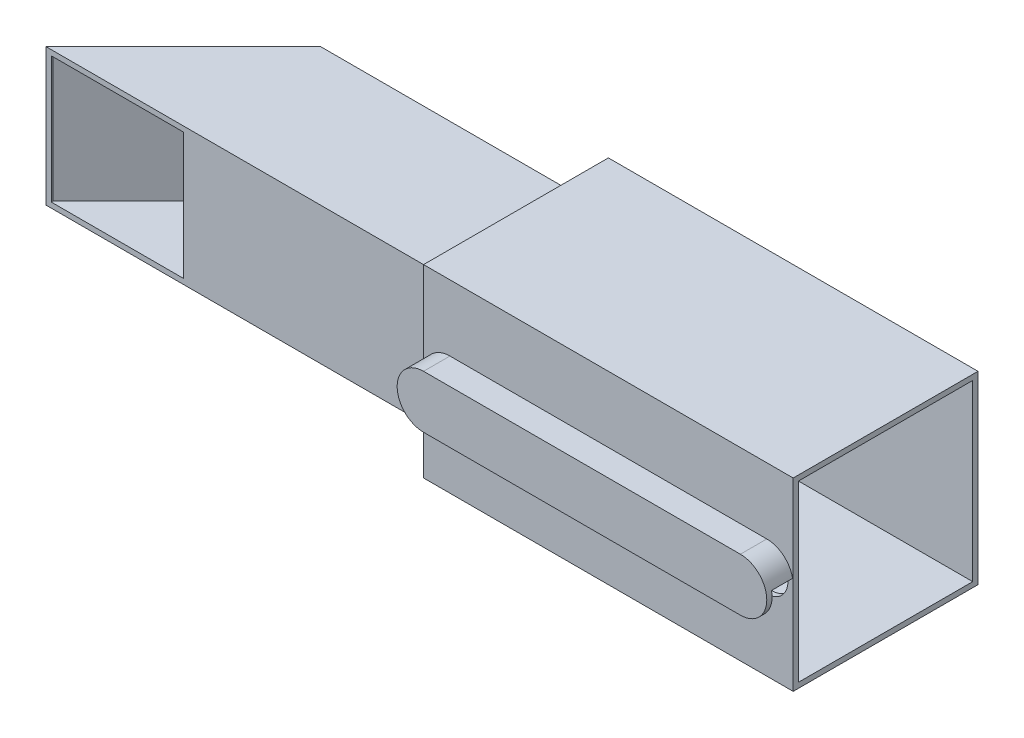
SolidWorks part; units mm, degrees
ref_plane "前视基准面" through (0, 0, 0) normal (0, 0, 1) x (1, 0, 0)
ref_plane "上视基准面" through (0, 0, 0) normal (0, 1, 0) x (1, 0, 0)
ref_plane "右视基准面" through (0, 0, 0) normal (1, 0, 0) x (0, 0, -1)
sketch "草图4" plane through (0, 0, 0) normal (0, 0, 1) x (1, 0, 0)
  line L0 (0, 17.5) -> (0, -17.5)
  line L1 (-30.7949, 0) -> (31.4954, 0) construction
  line L10 (70, 17.5) -> (70, -17.5)
  line L11 (70, -17.5) -> (0, -17.5)
  line L22 (70, 17.5) -> (0, 17.5)
  point P5 (70, 0)
  point P6 (0, 0)
  point P25 (70, 0)
  dimension "D3" = 35
  dimension "D7" = 70
extrude "凸台-拉伸6" add sketch "草图4" along normal mid plane 35
ref_plane "基准面2" through (0, 0, 22.5) normal (0, 0, 1) x (1, 0, 0)
sketch "草图6" plane through (0, 0, 22.5) normal (0, 0, 1) x (1, 0, 0)
  line L0 (72.5552, 0) -> (-4.6992, 0) construction
  line L1 (33.928, 22.6507) -> (33.928, -25.5555) construction
  line L2 (5, 5) -> (65, 5)
  line L3 (0, 17.5) -> (0, -17.5) construction
  line L4 (70, -17.5) -> (70, 17.5) construction
  line L5 (5, -5) -> (65, -5)
  arc A0 (5, 5) -> (5, -5) centre (5, 0) ccw
  arc A1 (65, -5) -> (65, 5) centre (65, 0) ccw
  dimension "D2" = 5
  dimension "D3" = 5
  dimension "D1" = 5
  dimension "D4" = 10
extrude "凸台-拉伸7" add sketch "草图6" against normal up to surface (5 mm away) up to face at (35, 0, 17.5)
shell "抽壳3" thickness 1 removed face at (70, 0, 3.5)
ref_plane "基准面3" through (5, 5, 22.5) normal (-1, 0, 0) x (0, 0, 1)
sketch "草图9" plane through (0, -5, 0) normal (0, -1, 0) x (1, 0, 0)
  line L0 (0, 21.5) -> (70, 21.5)
  line L1 (70, 17.5) -> (70, 21.5)
  line L2 (70, 17.5) -> (70, 22.5) construction
  line L3 (0, 17.5) -> (0, 21.5)
  line L4 (0, 17.5) -> (70, 17.5) construction
  line L5 (0, 17.5) -> (70, 17.5)
  dimension "D1" = 4
extrude "切除-拉伸1" cut sketch "草图9" against normal blind 6
sketch "草图22" plane through (0, 0, 0) normal (0, 0, 1) x (1, 0, 0)
  line L0 (0, -13) -> (0, 13)
  line L1 (0, 13) -> (-50, 13)
  line L2 (-50, 13) -> (-50, -13)
  line L3 (-60.5113, 0) -> (25.124, 0) construction
  line L4 (0, -13) -> (-50, -13)
  point P8 (0, 0)
  point P9 (-50, 0)
  dimension "D1" = 13
  dimension "D2" = 50
extrude "凸台-拉伸8" add sketch "草图22" along normal mid plane 26
shell "抽壳4" thickness 1 removed face at (-50, 0, 0)
sketch "草图23" plane through (0, 0, 0) normal (-1, 0, 0) x (0, 0, 1)
  line L0 (-12, 12) -> (12, 12) construction
  line L1 (-12, -12) -> (12, -12)
  line L2 (-12, -12) -> (-12, 12)
  line L3 (-12, 12) -> (12, 12)
  line L4 (12, -12) -> (12, 12)
  line L5 (12, -12) -> (12, 12) construction
extrude "切除-拉伸3" cut sketch "草图23" against normal up to surface (1 mm away) up to face at (1, 0, 3.3)
sketch "草图28" plane through (0, 0, 0) normal (0, 1, 0) x (1, 0, 0)
  line L0 (-88.544, 0) -> (82.1551, 0) construction
  line L5 (-50, 13) -> (-50, -13)
  line L6 (-50, -13) -> (-76, -13)
  line L7 (-76, -13) -> (-50, 13)
  line L8 (-50, 19.341) -> (-50, -26.0276) construction
  dimension "D1" = 45
extrude "凸台-拉伸11" add sketch "草图28" along normal mid plane 26
sketch "草图38" plane through (-50, 0, 0) normal (1, 0, 0) x (0, 0, -1)
  line L5 (-12, -12) -> (12, -12)
  line L6 (-12, -12) -> (-12, 12)
  line L7 (-12, 12) -> (12, 12)
  line L8 (12, -12) -> (12, 12)
shell "抽壳13" thickness 1 removed face at (-50, 0, 0)
sketch "草图40" plane through (0, 0, 13) normal (0, 0, 1) x (1, 0, 0)
  line L0 (-75, 12) -> (-75, -12)
  line L1 (-75, -12) -> (-50, -12)
  line L2 (-50, -12) -> (-50, 12)
  line L3 (-50, 12) -> (-75, 12)
  line L4 (-76, 13) -> (-76, -13) construction
  line L5 (0, 13) -> (-76, 13) construction
  line L6 (-76, -13) -> (0, -13) construction
  dimension "D1" = 1
  dimension "D2" = 1
  dimension "D3" = 1
  dimension "D4" = 25
extrude "切除-拉伸16" cut sketch "草图40" against normal offset from surface (25.2929 mm away) 0.5 up to face at (-63, 0, 0)
